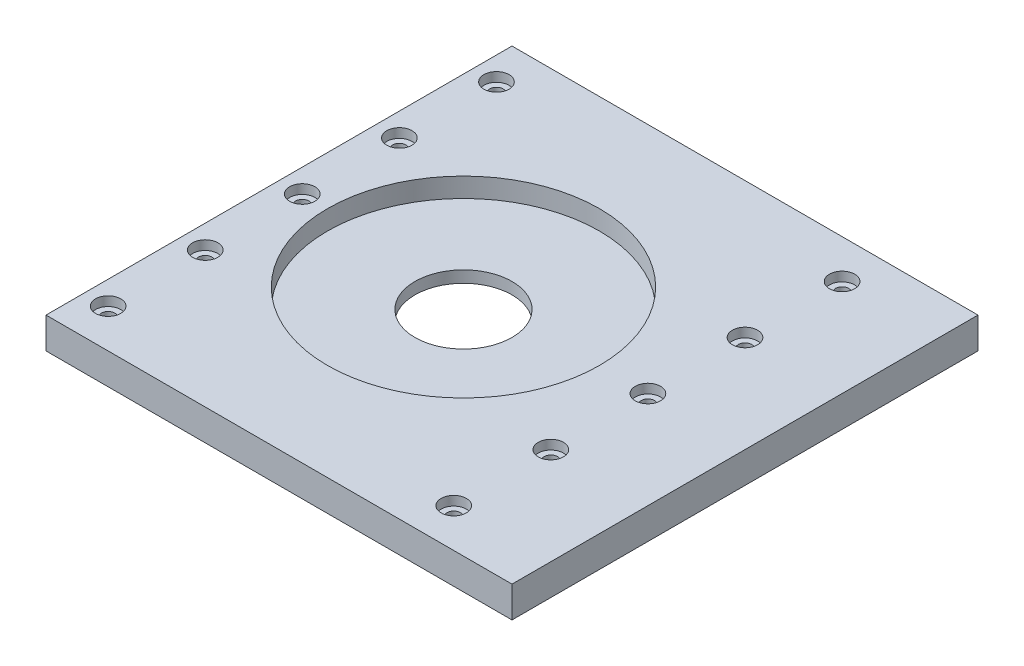
SolidWorks part; units mm, degrees
material "6061-T6 (SS)"
ref_plane "Front Plane" through (0, 0, 0) normal (0, 0, 1) x (1, 0, 0)
ref_plane "Top Plane" through (0, 0, 0) normal (0, 1, 0) x (1, 0, 0)
ref_plane "Right Plane" through (0, 0, 0) normal (1, 0, 0) x (0, 0, -1)
sketch "Sketch1" plane through (0, 0, 0) normal (0, 1, 0) x (1, 0, 0)
  line L1 (0, 0) -> (120, 0)
  line L2 (0, 0) -> (0, 120)
  line L3 (0, 120) -> (120, 120)
  line L4 (120, 0) -> (120, 120)
  dimension "D1" = 120
extrude "Boss-Extrude1" add sketch "Sketch1" along normal blind 8
sketch "Sketch2" plane through (0, 8, 0) normal (0, 1, 0) x (1, 0, 0)
  line L0 (0, 120) -> (6, 120)
  line L1 (120, 120) -> (0, 120) construction
  line L2 (6, 120) -> (6, 0)
  line L3 (0, 0) -> (120, 0) construction
  line L4 (0, 120) -> (0, 0) construction
  line L5 (95, 120) -> (95, 0) construction
  line L7 (120, 0) -> (120, 120) construction
  point P11 (6, 110)
  point P18 (6, 85)
  point P19 (6, 60)
  point P20 (6, 35)
  point P21 (6, 10)
  point P32 (95, 60)
  point P41 (95, 35)
  point P42 (95, 10)
  point P43 (95, 60)
  point P44 (95, 35)
  point P45 (95, 85)
  point P46 (95, 60)
  point P47 (95, 85)
  point P48 (95, 110)
  dimension "D1" = 5
  dimension "D2" = 10
  dimension "D3" = 6
  dimension "D4" = 25
  dimension "D5" = 3
  dimension "D6" = 3
hole_wizard "CBORE for M3 Hex Socket Thin Head Cap Screw1" positions "Sketch2" profile "Sketch3" counterbore size "M3" standard "DIN" end condition through all
sketch "Sketch3" plane through (95, 8, -110) normal (1, 0, 0) x (0, 0, 1)
  line L0 (0, 0) -> (0, 8)
  line L1 (0, 8) -> (1.7, 8)
  line L3 (1.7, 8) -> (1.7, 2.4)
  line L4 (1.7, 2.4) -> (3.25, 2.4)
  line L5 (3.25, 2.4) -> (3.25, 0)
  line L7 (3.25, 0) -> (0, 0)
  line L11 (0, -6.35) -> (0, 107.95) construction
  dimension "Thru Hole Dia." = 3.4
  dimension "Thru Hole Depth" = 8
  dimension "C'Bore Dia." = 6.5
  dimension "C'Bore Depth" = 2.4
sketch "Sketch6" plane through (0, 8, 0) normal (0, 1, 0) x (1, 0, 0)
  line L0 (6, 110) -> (95, 10) construction
  line L1 (95, 10) -> (95, 120)
  line L2 (120, 120) -> (0, 120) construction
  line L3 (95, 120) -> (0, 0)
  line L4 (0, 0) -> (0, 120)
  line L5 (0, 120) -> (96, 0)
  line L6 (0, 0) -> (120, 0) construction
  point P19 (47.5, 60)
hole_wizard "Ø25.0mm Dowel Hole1" positions "Sketch6" profile "Sketch5" hole size "Ø25.0" standard "DIN"
sketch "Sketch5" plane through (47.5, 8, -60) normal (1, 0, 0) x (0, 0, 1)
  line L0 (0, 0) -> (0, 17.5108)
  line L1 (0, 17.5108) -> (12.5, 10)
  line L2 (12.5, 10) -> (12.5, 0)
  line L5 (12.5, 0) -> (0, 0)
  line L10 (0, 17.5108) -> (-12.5, 10) construction
  line L11 (0, -6.35) -> (0, 107.95) construction
  dimension "Hole Dia." = 25
  dimension "Hole Depth" = 10
  dimension "Drill Angle" = 118
sketch "Sketch7" plane through (0, 8, 0) normal (0, 1, 0) x (1, 0, 0)
  circle A0 centre (47.5, 60) radius 35
  dimension "D1" = 70
extrude "Cut-Extrude1" cut sketch "Sketch7" against normal blind 5
